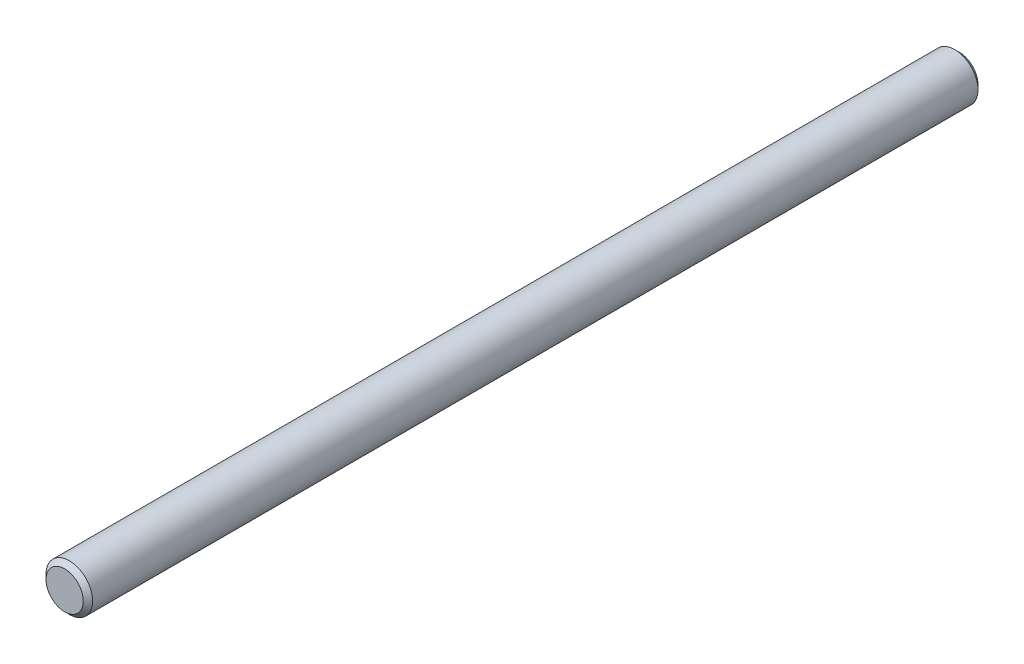
SolidWorks part; units mm, degrees
ref_plane "Front" through (0, 0, 0) normal (0, 0, 1) x (1, 0, 0)
ref_plane "Top" through (0, 0, 0) normal (0, 1, 0) x (1, 0, 0)
ref_plane "Right" through (0, 0, 0) normal (1, 0, 0) x (0, 0, -1)
sketch "Sketch1" plane through (0, 0, 0) normal (0, 0, 1) x (1, 0, 0)
  circle A0 centre (0, 0) radius 7.9375
  dimension "dia" = 15.875
extrude "Extrude1" add sketch "Sketch1" along normal mid plane 304.8
sketch "Sketch2" plane through (0, 0, 0) normal (1, 0, 0) x (0, 0, -1)
  line L0 (-152.4, 7.9375) -> (-152.4, -7.9375) construction
  line L1 (152.4, 7.9375) -> (152.4, -7.9375) construction
  point P0 (-152.4, 7.9375)
  point P1 (152.4, 7.9375)
chamfer "Chamfer1" distance 1.5875 angle 45 2 edges at (7.9375, 0, -152.4) (7.9375, 0, 152.4)
equation "\"D1@Chamfer1\" = \"dia@Sketch1\" * .1"
